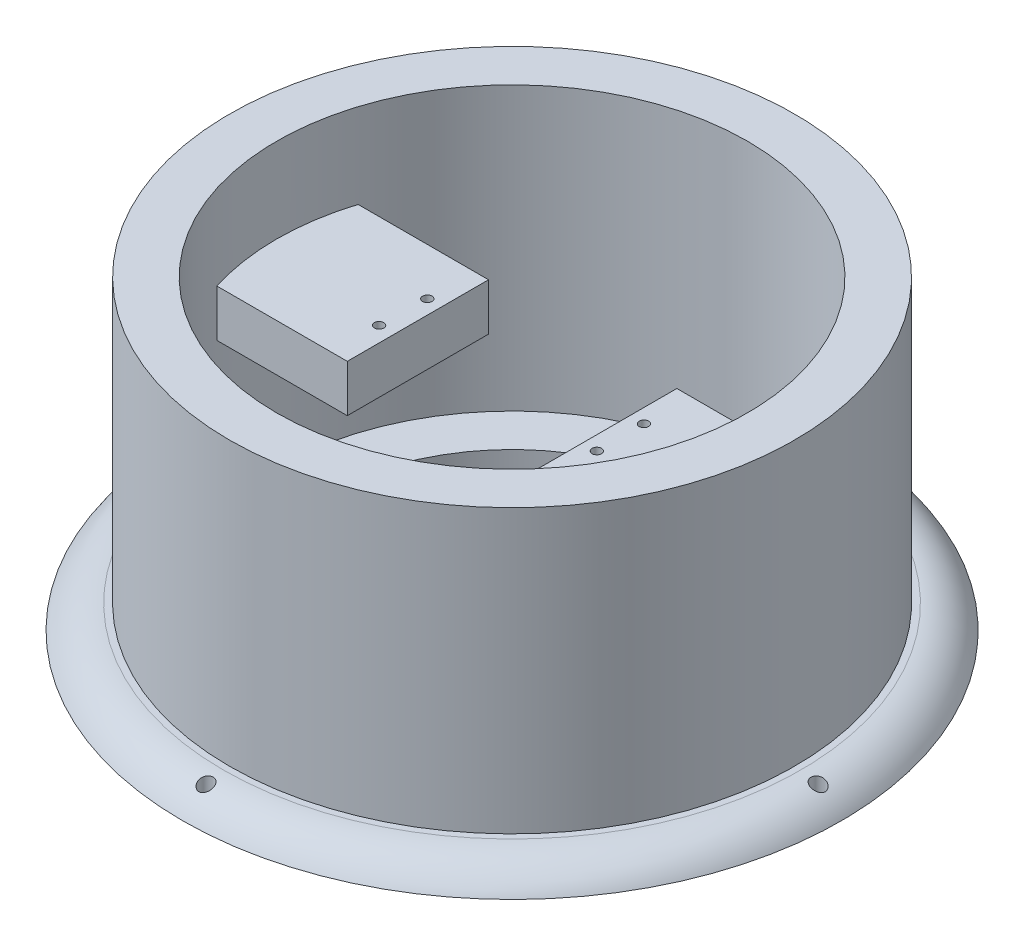
SolidWorks part; units mm, degrees
ref_plane "Front Plane" through (0, 0, 0) normal (0, 0, 1) x (1, 0, 0)
ref_plane "Top Plane" through (0, 0, 0) normal (0, 1, 0) x (1, 0, 0)
ref_plane "Right Plane" through (0, 0, 0) normal (1, 0, 0) x (0, 0, -1)
sketch "Sketch1" plane through (0, 0, 0) normal (0, 1, 0) x (1, 0, 0)
  circle A0 centre (0, 0) radius 60
  dimension "D1" = 120
extrude "Boss-Extrude1" add sketch "Sketch1" along normal blind 60
shell "Shell1" thickness 10 removed face at (0, 0, 60) removed face at (0, 60, 60)
sketch "Sketch2" plane through (0, 0, 0) normal (0, 1, 0) x (1, 0, 0)
  circle A1 centre (0, 0) radius 70
  dimension "D1" = 140
extrude "Boss-Extrude2" add sketch "Sketch2" against normal blind 5
sketch "Sketch5" plane through (0, 0, 0) normal (0, 1, 0) x (1, 0, 0)
  circle A0 centre (0, 0) radius 40
  dimension "D1" = 80
extrude "Cut-Extrude4" cut sketch "Sketch5" against normal blind 5
fillet "Fillet1" radius 10 1 edges at (0, 0, 70)
sketch "Sketch7" plane through (0, 0, 0) normal (1, 0, 0) x (0, 0, -1)
  line L0 (60, 0) -> (60, 60) construction
  line L1 (-15, 42) -> (15, 42)
  line L2 (-15, 42) -> (-15, 32)
  line L3 (-15, 32) -> (15, 32)
  line L4 (15, 42) -> (15, 32)
  line L5 (-60, 60) -> (-60, 0) construction
  line L6 (50, 60) -> (-50, 60) construction
  dimension "D1" = 45
  dimension "D2" = 30
  dimension "D3" = 45
  dimension "D4" = 10
  dimension "D5" = 18
extrude "Boss-Extrude4" add sketch "Sketch7" along normal blind 55 and the other way blind 54
sketch "Sketch8" plane through (0, 0, 0) normal (0, 1, 0) x (1, 0, 0)
  line L1 (-20, 16) -> (20, 16)
  line L2 (-20, 16) -> (-20, -16)
  line L3 (-20, -16) -> (20, -16)
  line L4 (20, 16) -> (20, -16)
  line L5 (-20, 16) -> (20, -16) construction
  line L6 (-20, -16) -> (20, 16) construction
  point P0 (0, 0)
  dimension "D1" = 40
  dimension "D2" = 32
extrude "Cut-Extrude6" cut sketch "Sketch8" along normal blind 55
sketch "Sketch9" plane through (0, 0, 0) normal (0, 1, 0) x (1, 0, 0)
  line L0 (-47.697, 15) -> (-20, 15) construction
  line L1 (-47.697, -15) -> (-20, -15) construction
  line L2 (-20, -15) -> (-20, 15) construction
  line L3 (20, 15) -> (20, -15) construction
  circle A0 centre (-23, 5) radius 1
  circle A1 centre (-23.2366, -5) radius 1
  circle A2 centre (23, 5) radius 1
  circle A3 centre (23, -5) radius 1
  dimension "D1" = 2
  dimension "D2" = 2
  dimension "D3" = 10
  dimension "D4" = 10
  dimension "D5" = 10
  dimension "D6" = 3
  dimension "D7" = 2
  dimension "D8" = 2
  dimension "D10" = 3
  dimension "D9" = 3
extrude "Cut-Extrude7" cut sketch "Sketch9" along normal blind 55
ref_plane "Plane1" through (0, 0, 0) normal (0, 1, 0) x (1, 0, 0)
sketch "Sketch10" plane through (0, 0, 0) normal (0, 1, 0) x (1, 0, 0)
  circle A0 centre (0, 65) radius 1.5
  circle A1 centre (0, 0) radius 70 construction
  circle A2 centre (65, 0) radius 1.5
  circle A3 centre (0, -65) radius 1.5
  circle A4 centre (-65, 0) radius 1.5
  dimension "D1" = 3
  dimension "D2" = 65
  dimension "D3" = 3
  dimension "D4" = 65
  dimension "D5" = 3
  dimension "D6" = 65
  dimension "D7" = 3
  dimension "D8" = 65
extrude "Cut-Extrude8" cut sketch "Sketch10" against normal blind 30
